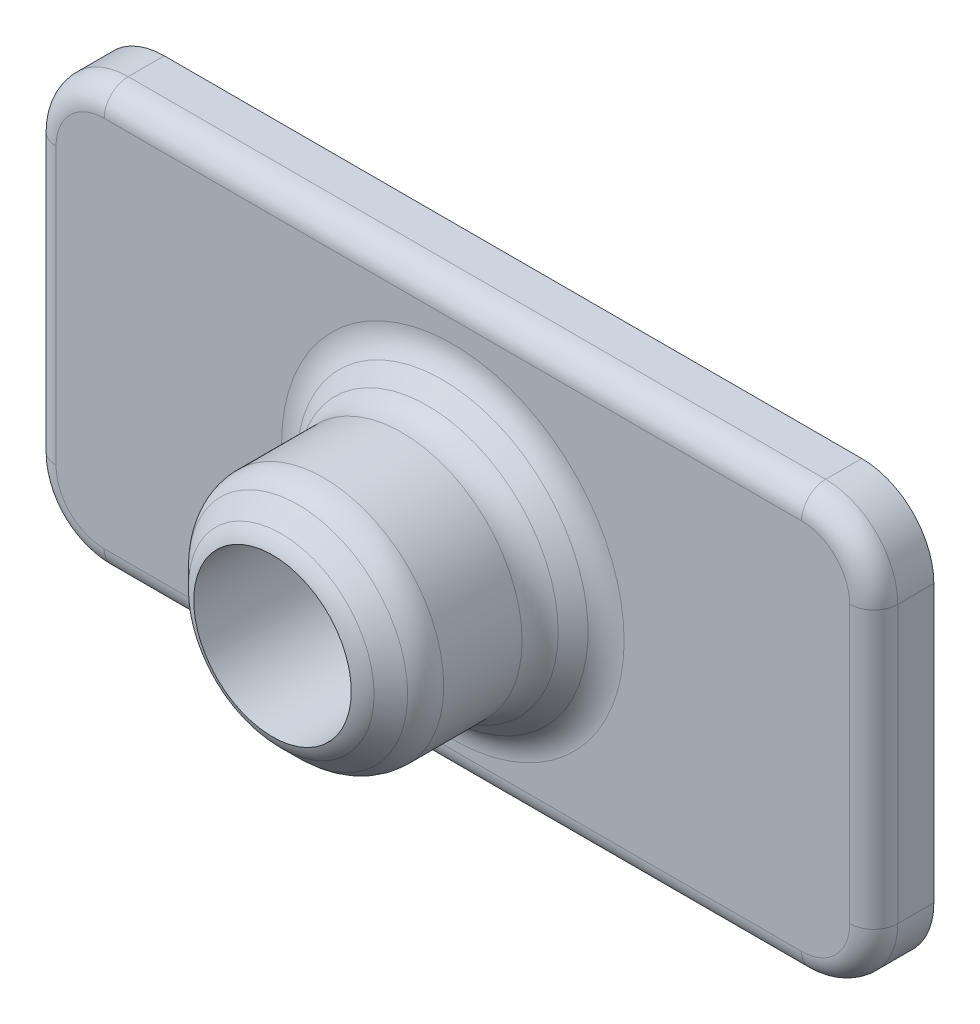
SolidWorks part; units mm, degrees
ref_plane "Front Plane" through (0, 0, 0) normal (0, 0, 1) x (1, 0, 0)
ref_plane "Top Plane" through (0, 0, 0) normal (0, 1, 0) x (1, 0, 0)
ref_plane "Right Plane" through (0, 0, 0) normal (1, 0, 0) x (0, 0, -1)
sketch "Sketch1" plane through (0, 0, 0) normal (0, 0, 1) x (1, 0, 0)
  line L1 (-115, -75) -> (-45, -75)
  line L2 (-115, -75) -> (-115, -40)
  line L3 (-115, -40) -> (-45, -40)
  line L4 (-45, -40) -> (-45, -75)
extrude "Boss-Extrude1" add sketch "Sketch1" along normal blind 5
fillet "Fillet1" radius 6 4 edges at (-45, -40, 2.5) (-45, -75, 2.5) (-115, -75, 2.5) (-115, -40, 2.5)
sketch "Sketch2" plane through (0, 0, 5) normal (0, 0, 1) x (1, 0, 0)
  circle A0 centre (-80, -58) radius 6.55
  circle A1 centre (-80, -58) radius 10
extrude "Boss-Extrude2" add sketch "Sketch2" along normal blind 15
chamfer "Chamfer1" distance 3 angle 45 2 edges at (-90, -58, 5) (-70, -58, 20)
fillet "Fillet2" radius 3 4 edges at (-93, -58, 5) (-90, -58, 8) (-73, -58, 20) (-70, -58, 17)
fillet "Fillet3" radius 2 8 edges at (-113.2426, -41.7574, 5) (-80, -40, 5) (-46.7574, -41.7574, 5) (-45, -57.5, 5) (-46.7574, -73.2426, 5) (-80, -75, 5) (-113.2426, -73.2426, 5) (-115, -57.5, 5)
